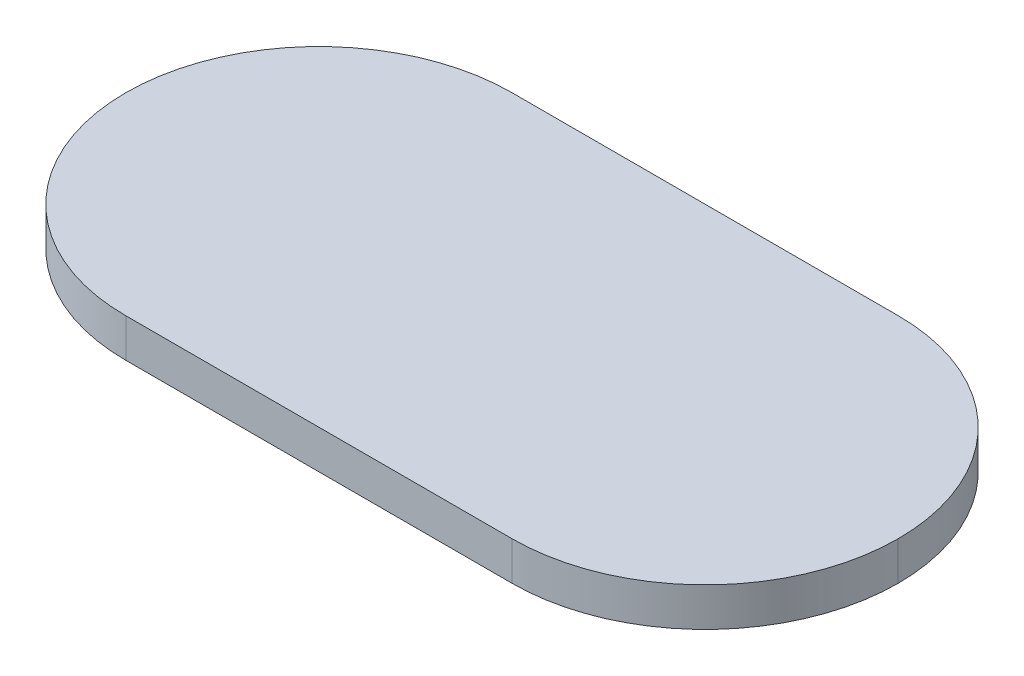
SolidWorks part; units mm, degrees
ref_plane "Front Plane" through (0, 0, 0) normal (0, 0, 1) x (1, 0, 0)
ref_plane "Top Plane" through (0, 0, 0) normal (0, 1, 0) x (1, 0, 0)
ref_plane "Right Plane" through (0, 0, 0) normal (1, 0, 0) x (0, 0, -1)
sketch "Sketch1" plane through (0, 0, 0) normal (0, 1, 0) x (1, 0, 0)
  line L1 (-100, 50) -> (100, 50)
  line L2 (-100, 50) -> (-100, -50)
  line L3 (-100, -50) -> (100, -50)
  line L4 (100, 50) -> (100, -50)
  line L5 (-100, 50) -> (100, -50) construction
  line L6 (-100, -50) -> (100, 50) construction
  point P0 (0, 0)
  dimension "D1" = 100
  dimension "D2" = 200
extrude "Boss-Extrude1" add sketch "Sketch1" along normal blind 10
fillet "Fillet1" radius 50 4 edges at (100, 5, -50) (100, 5, 50) (-100, 5, 50) (-100, 5, -50)
sketch "Sketch2" plane through (0, 10, 0) normal (0, 1, 0) x (1, 0, 0)
  line L1 (-67.0906, 40.8911) -> (-19.5906, 40.8911)
  line L2 (-67.0906, 40.8911) -> (-67.0906, -3.1089)
  line L3 (-67.0906, -3.1089) -> (-19.5906, -3.1089)
  line L4 (-19.5906, 40.8911) -> (-19.5906, -3.1089)
  line L5 (-67.0906, 40.8911) -> (-19.5906, -3.1089) construction
  line L6 (-67.0906, -3.1089) -> (-19.5906, 40.8911) construction
  point P0 (-43.3406, 18.8911)
  dimension "D1" = 44
  dimension "D2" = 47.5
